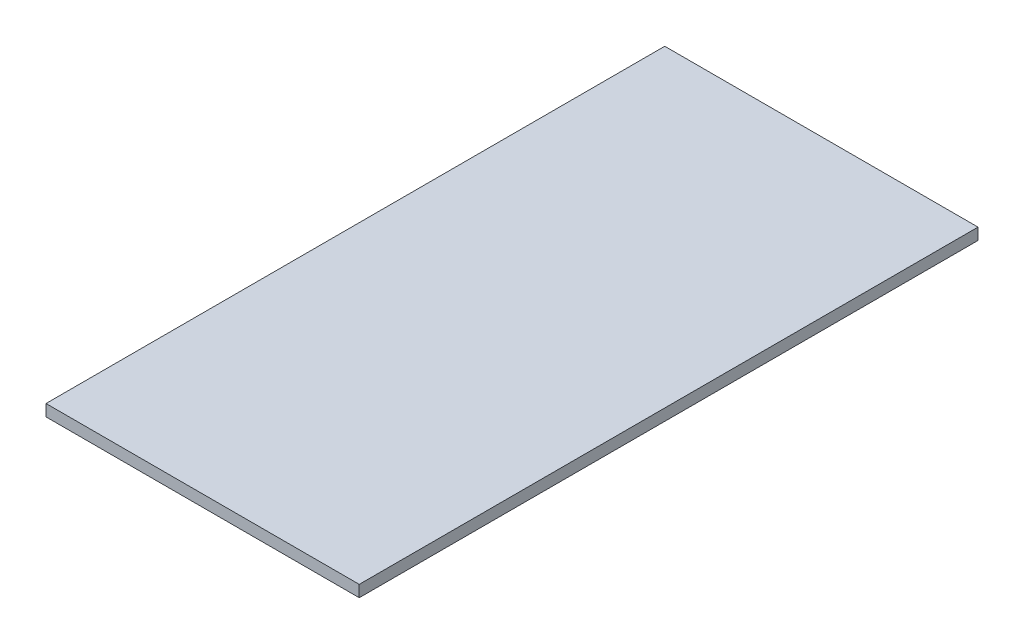
SolidWorks part; units mm, degrees
material "아크릴(내충격성)"
ref_plane "정면" through (0, 0, 0) normal (0, 0, 1) x (1, 0, 0)
ref_plane "윗면" through (0, 0, 0) normal (0, 1, 0) x (1, 0, 0)
ref_plane "우측면" through (0, 0, 0) normal (1, 0, 0) x (0, 0, -1)
sketch "스케치1" plane through (0, 0, 0) normal (0, 1, 0) x (1, 0, 0)
  line L1 (-40.5, 80) -> (40.5, 80)
  line L2 (-40.5, 80) -> (-40.5, -80)
  line L3 (-40.5, -80) -> (40.5, -80)
  line L4 (40.5, 80) -> (40.5, -80)
  line L5 (-40.5, 80) -> (40.5, -80) construction
  line L6 (-40.5, -80) -> (40.5, 80) construction
  point P0 (0, 0)
  dimension "D1" = 81
  dimension "D2" = 160
extrude "보스-돌출1" add sketch "스케치1" along normal blind 3
